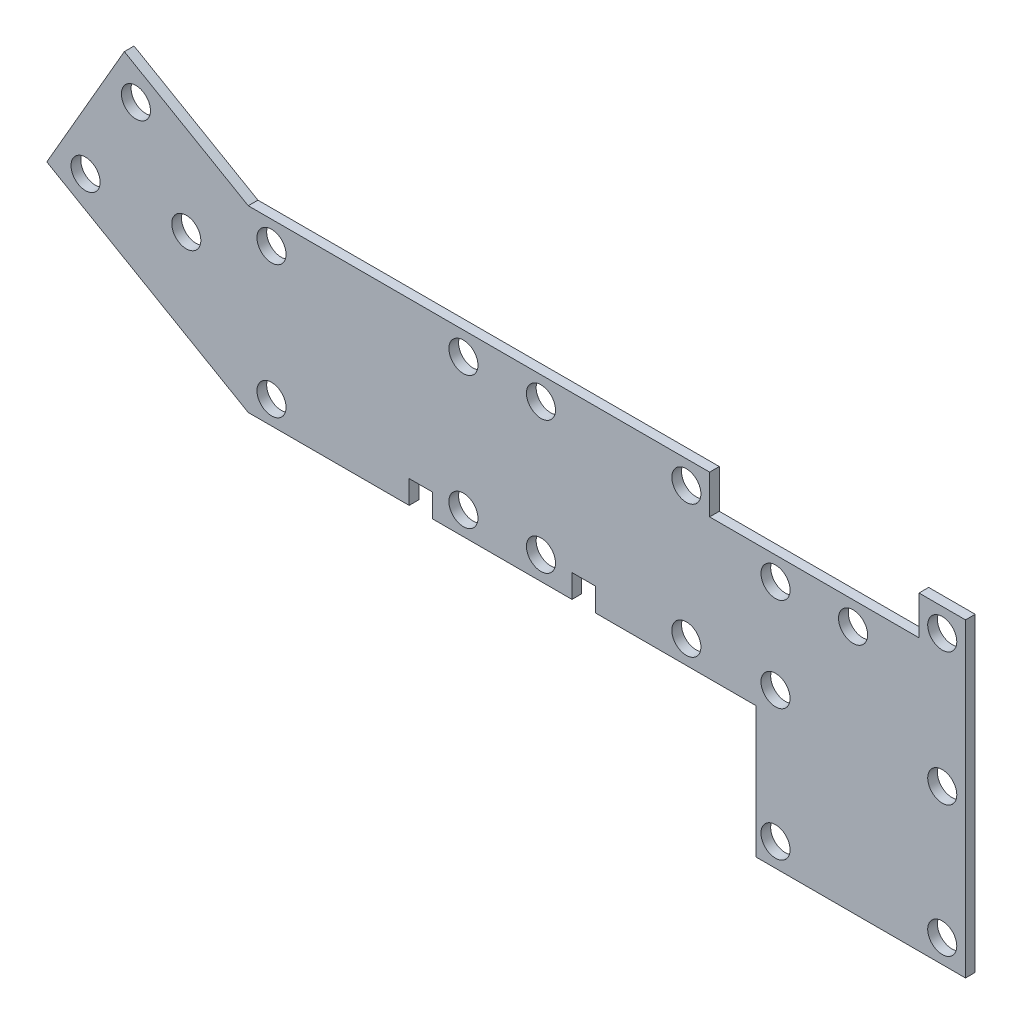
SolidWorks part; units mm, degrees
material "1023 Carbon Steel Sheet (SS)"
ref_plane "Front Plane" through (0, 0, 0) normal (0, 0, 1) x (1, 0, 0)
ref_plane "Top Plane" through (0, 0, 0) normal (0, 1, 0) x (1, 0, 0)
ref_plane "Right Plane" through (0, 0, 0) normal (1, 0, 0) x (0, 0, -1)
sketch "Sketch1" plane through (0, 0, 0) normal (0, 0, 1) x (1, 0, 0)
  line L0 (0, 0) -> (-40.5911, 23.4353)
  line L1 (-40.5911, 23.4353) -> (-65.9911, -20.5588)
  line L2 (-65.9911, -20.5588) -> (0, -58.6588)
  line L3 (0, -58.6588) -> (52.705, -58.6588)
  line L4 (52.705, -58.6588) -> (52.705, -51.0388)
  line L5 (52.705, -51.0388) -> (60.325, -51.0388)
  line L6 (60.325, -51.0388) -> (60.325, -58.6588)
  line L7 (60.325, -58.6588) -> (106.045, -58.6588)
  line L8 (106.045, -58.6588) -> (106.045, -51.0388)
  line L9 (106.045, -51.0388) -> (113.665, -51.0388)
  line L10 (113.665, -51.0388) -> (113.665, -58.6588)
  line L11 (113.665, -58.6588) -> (166.37, -58.6588)
  line L12 (166.37, -58.6588) -> (166.37, -101.6)
  line L13 (166.37, -101.6) -> (234.95, -101.6)
  line L14 (234.95, -101.6) -> (234.95, 0)
  line L15 (234.95, 0) -> (219.71, 0)
  line L16 (219.71, 0) -> (219.71, -12.7)
  line L17 (219.71, -12.7) -> (151.13, -12.7)
  line L18 (151.13, -12.7) -> (151.13, 0)
  line L19 (151.13, 0) -> (113.03, 0)
  line L23 (113.03, 0) -> (0, 0)
  circle A1 centre (-20.2956, -17.6117) radius 4.7625
  circle A2 centre (-53.2911, -17.6117) radius 4.7625
  circle A3 centre (-36.7934, 10.9633) radius 4.7625
  circle A4 centre (-36.7934, -8.0867) radius 19.05 construction
  circle A5 centre (7.62, -51.0388) radius 4.7625
  circle A6 centre (7.62, -7.62) radius 4.7625
  circle A7 centre (70.485, -7.62) radius 4.7625
  circle A8 centre (95.885, -7.62) radius 4.7625
  circle A9 centre (143.51, -7.62) radius 4.7625
  circle A10 centre (95.885, -51.0388) radius 4.7625
  circle A11 centre (70.485, -51.0388) radius 4.7625
  circle A12 centre (143.51, -51.0388) radius 4.7625
  circle A13 centre (172.72, -20.32) radius 4.7625
  circle A14 centre (198.12, -20.32) radius 4.7625
  circle A15 centre (227.33, -7.62) radius 4.7625
  circle A16 centre (227.33, -93.98) radius 4.7625
  circle A17 centre (172.72, -93.98) radius 4.7625
  circle A18 centre (227.33, -51.0388) radius 4.7625
  circle A19 centre (172.72, -51.0388) radius 4.7625
  point P3 (-36.7934, -8.0867)
  point P24 (185.42, -12.7)
  point P28 (-53.2911, 1.4383)
  point P33 (83.185, -58.6588)
  dimension "D18" = 9.525
  dimension "D21" = 3
  dimension "D16" = 38.1
  dimension "D17" = 7.62
  dimension "D1" = 30
  dimension "D2" = 76.2
  dimension "D3" = 50.8
  dimension "D4" = 83.185
  dimension "D5" = 68.58
  dimension "D6" = 7.62
  dimension "D7" = 7.62
  dimension "D8" = 45.72
  dimension "D9" = 166.37
  dimension "D10" = 7.62
  dimension "D11" = 19.05
  dimension "D12" = 38.1
  dimension "D13" = 101.6
  dimension "D14" = 15.24
  dimension "D15" = 12.7
  dimension "D19" = 19.05
  dimension "D20" = 25.4
  dimension "D22" = 7.62
  dimension "D23" = 7.62
  dimension "D24" = 12.7
  dimension "D25" = 12.7
  dimension "D26" = 7.62
  dimension "D27" = 7.62
  dimension "D28" = 12.7
  dimension "D29" = 12.7
  dimension "D30" = 7.62
  dimension "D31" = 7.62
  dimension "D32" = 7.62
extrude "Boss-Extrude1" add sketch "Sketch1" along normal blind 3.175 contours L19 L23 L0 L1 L2 L3 L4 L5 L6 L7 L8 L9 L10 L11 L12 L13 L14 L15 L16 L17 L18 A19 A18 A17 A16 A15 A14 A13 A12 A11 A10 A9 A8 A7 A6 A5 region at (103.3328, -36.1541, 0)
